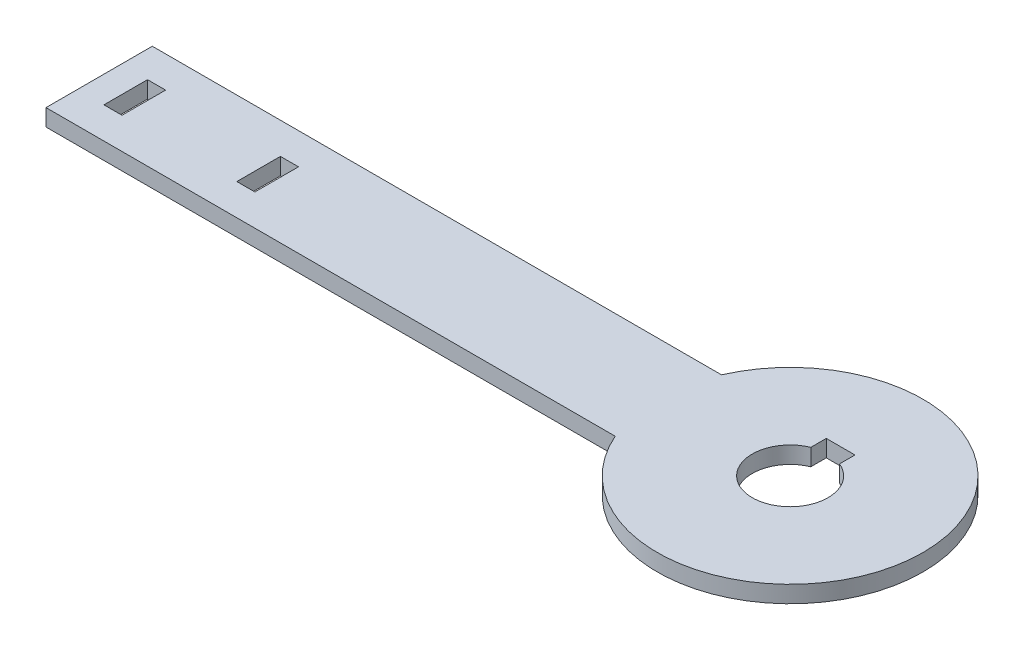
SolidWorks part; units mm, degrees
ref_plane "Front Plane" through (0, 0, 0) normal (0, 0, 1) x (1, 0, 0)
ref_plane "Top Plane" through (0, 0, 0) normal (0, 1, 0) x (1, 0, 0)
ref_plane "Right Plane" through (0, 0, 0) normal (1, 0, 0) x (0, 0, -1)
sketch "Sketch1" plane through (0, 0, 0) normal (0, 1, 0) x (1, 0, 0)
  line L0 (-22.9129, 0) -> (-125, 0) construction
  line L7 (-22.9129, -10) -> (-125, -10)
  line L8 (-22.9129, 10) -> (-125, 10)
  line L9 (-22.9129, 0) -> (0, 0) construction
  line L14 (-22.9129, 10) -> (-22.9129, -10) construction
  line L15 (-125, 10) -> (-125, -10) construction
  line L17 (-2.7, 6.5936) -> (-2.7, 9.5)
  line L18 (-2.7, 9.5) -> (2.7, 9.5)
  line L19 (2.7, 9.5) -> (2.7, 6.5936)
  line L20 (0, 0) -> (0, 9.5) construction
  line L21 (0, 32.5) -> (0, 0) construction
  line L22 (0, 0) -> (32.5, 0) construction
  line L23 (-125, 4.1) -> (-125, -4.1)
  line L24 (0, -32.5) -> (0, 0) construction
  line L28 (-125, 10) -> (-130, 10)
  line L29 (-130, 10) -> (-130, -10)
  line L30 (-130, -10) -> (-125, -10)
  line L31 (-125, 4.1) -> (-121.6, 4.1)
  line L32 (-121.6, 4.1) -> (-121.6, -4.1)
  line L33 (-121.6, -4.1) -> (-125, -4.1)
  line L34 (-100, 4.1) -> (-100, -4.1)
  line L35 (-100, -4.1) -> (-96.6, -4.1)
  line L36 (-96.6, -4.1) -> (-96.6, 4.1)
  line L37 (-96.6, 4.1) -> (-100, 4.1)
  arc A0 (-2.7, 6.5936) -> (2.7, 6.5936) centre (0, 0) ccw
  circle A1 centre (0, 0) radius 32.5 construction
  circle A10 centre (-85, 0) radius 1.5 construction
  circle A12 centre (0, 0) radius 25
  point P3 (-84.3436, 0)
  point P4 (0, 0)
  point P5 (-96.8, -4.05)
  dimension "D1" = 14.25
  dimension "D2" = 65
  dimension "D5" = 5
  dimension "D11" = 9.5
  dimension "D15" = 3
  dimension "D3" = 50
  dimension "D4" = 130
  dimension "D6" = 8.2
  dimension "D7" = 20
  dimension "D8" = 15
  dimension "D10" = 5.4
  dimension "D14" = 3.4
  dimension "D16" = 25
extrude "Boss-Extrude1" add sketch "Sketch1" along normal blind 3.175 contours A12 L8 L28 L29 L30 L7 L32 L33 L23 L31 L37 L36 L35 L34 A10 | A12 A0 L17 L18 L19 region at (-76.2448, 0, 0) region at (-24.2929, 0, 0)
